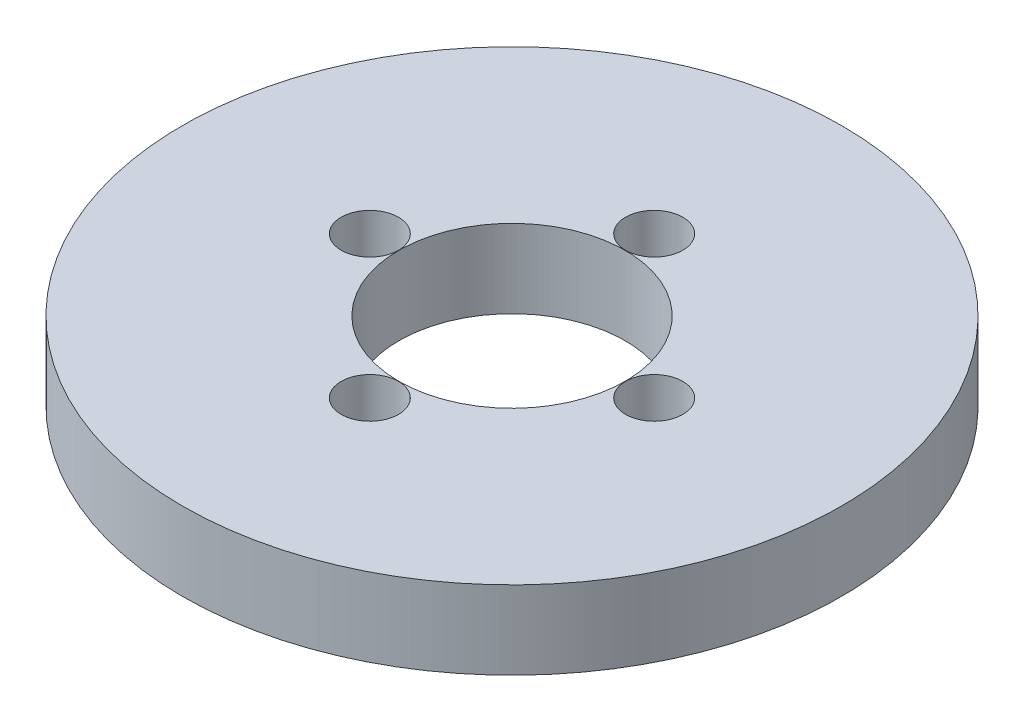
SolidWorks part; units mm, degrees
ref_plane "Front Plane" through (0, 0, 0) normal (0, 0, 1) x (1, 0, 0)
ref_plane "Top Plane" through (0, 0, 0) normal (0, 1, 0) x (1, 0, 0)
ref_plane "Right Plane" through (0, 0, 0) normal (1, 0, 0) x (0, 0, -1)
sketch "Sketch1" plane through (0, 0, 0) normal (0, 1, 0) x (1, 0, 0)
  circle A0 centre (0, 0) radius 80
  dimension "FLANGE_OD" = 160
extrude "Boss-Extrude1" add sketch "Sketch1" along normal blind 19
sketch "Sketch2" plane through (0, 0, 0) normal (0, 1, 0) x (1, 0, 0)
  circle A0 centre (0, 0) radius 27.5
  dimension "BORE_D" = 55
extrude "Cut-Extrude1" cut sketch "Sketch2" along normal through all
sketch "Sketch3" plane through (0, 19, 0) normal (0, 1, 0) x (1, 0, 0)
  circle A0 centre (0, 0) radius 34.5149 construction
  circle A1 centre (-34.5149, 0) radius 6.9543
  dimension "BOLT_D" = 13.9086
  dimension "BOLT_PCD" = 69.0298
extrude "Cut-Extrude2" cut sketch "Sketch3" against normal blind 13.1453
pattern_circular "CirPattern1" count 4 over 360 about axis through (0, 0, 0) along (0, 1, 0) of "Cut-Extrude2"
